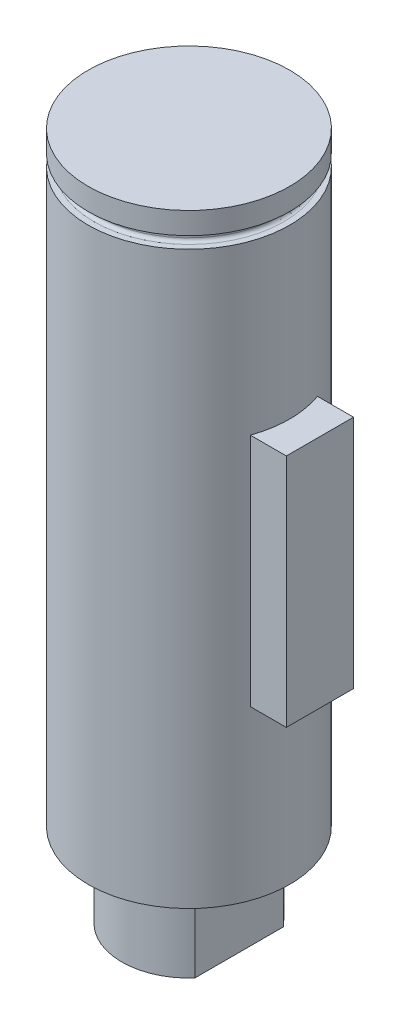
SolidWorks part; units mm, degrees
note: '?' marks a value the reader was unsure of.
ref_plane "前视基准面" through (0, 0, 0) normal (0, 0, 1) x (1, 0, 0)
ref_plane "上视基准面" through (0, 0, 0) normal (0, 1, 0) x (1, 0, 0)
ref_plane "右视基准面" through (0, 0, 0) normal (1, 0, 0) x (0, 0, -1)
sketch "Sketch1" plane through (0, 0, 0) normal (0, 1, 0) x (1, 0, 0)
  line L0 (7.8, -2) -> (7.8, 2)
  line L1 (-8.4121, 0) -> (5, 0) construction
  line L4 (7.8, 0) -> (13.7509, 0) construction
  line L5 (7.8, 2) -> (5.6569, 2)
  line L6 (7.8, -2) -> (5.6569, -2)
  arc A0 (5.6569, 2) -> (5.6569, -2) centre (0, 0) ccw
  point P8 (7.8, 0)
  dimension "D1" = 2
  dimension "D3" = 6
  dimension "D2" = 7.8
extrude "Boss-Extrude1" add sketch "Sketch1" along normal blind 14
sketch "Sketch2" plane through (0, 14, 0) normal (0, 1, 0) x (1, 0, 0)
  circle A0 centre (0, 0) radius 6
  dimension "D1" = 12
extrude "Boss-Extrude2" add sketch "Sketch2" along normal blind 12
sketch "Sketch3" plane through (0, 0, 0) normal (0, -1, 0) x (1, 0, 0)
  circle A0 centre (0, 0) radius 6
  dimension "D1" = 12
extrude "Boss-Extrude3" add sketch "Sketch3" along normal blind 10
sketch "Sketch4" plane through (0, -10, 0) normal (0, -1, 0) x (1, 0, 0)
  circle A0 centre (0, 0) radius 1.5
extrude "Cut-Extrude1" cut sketch "Sketch4" against normal blind 5
ref_plane "Plane6" through (0, 24.35, 0) normal (0, 1, 0) x (1, 0, 0)
sketch3d "3DSketch1"
  point P0 (5.8439, 5.7238, 1.3597)
ref_axis "Axis1" through (0, 26, 0) along (0, -1, 0)?
ref_plane "Plane5" through (0, 0, 0) normal (-0.2266, 0, 0.974) x (-0.2751, -0.9593, -0.064)
sketch "Groove Sketch" plane through (1.6043, 12.1829, 0.3733) normal (-0.2266, 0, 0.974) x (-0.9343, 0.2824, -0.2174)
  line L0 (10.5354, -9.9464) -> (11.9983, -9.5157)
  line L1 (11.9983, -9.5157) -> (11.8006, -8.8442)
  line L2 (11.8006, -8.8442) -> (10.3377, -9.2749)
  line L3 (10.2023, -9.5232) -> (10.2871, -9.811)
  line L4 (15.1493, -45.6204) -> (-11.9454, 46.402) construction
  line L5 (-0.273, -14.484) -> (11.2383, -11.0946) construction
  line L6 (5.4826, -12.7893) -> (-4.6855, 21.7449) construction
  arc A0 (10.2871, -9.811) -> (10.5354, -9.9464) centre (10.4789, -9.7545) ccw
  arc A1 (10.2023, -9.5232) -> (10.3377, -9.2749) centre (10.3942, -9.4668) cw
  point P10 (10.2447, -9.6671)
  dimension "Radius" = 0.2
  dimension "ID" = 10.9
  dimension "OD" = 14.35
  dimension "Width" = 0.7
  dimension "Location" = 1.65
revolve "Retaining Ring Groove" cut sketch "Groove Sketch" angle 360 about L4 reverse direction yes
other "c-ring<1>"
sketch "Sketch5" plane through (0, -10, 0) normal (0, -1, 0) x (1, 0, 0)
  line L0 (3, 1.4724) -> (3, -1.129) construction
  line L8 (3, -2.6458) -> (3, 2.6458)
  circle A1 centre (0, 0) radius 1.5
  arc A2 (3, 2.6458) -> (3, -2.6458) centre (0, 0) ccw
  dimension "D1" = 3
extrude "Boss-Extrude4" add sketch "Sketch5" along normal blind 5
